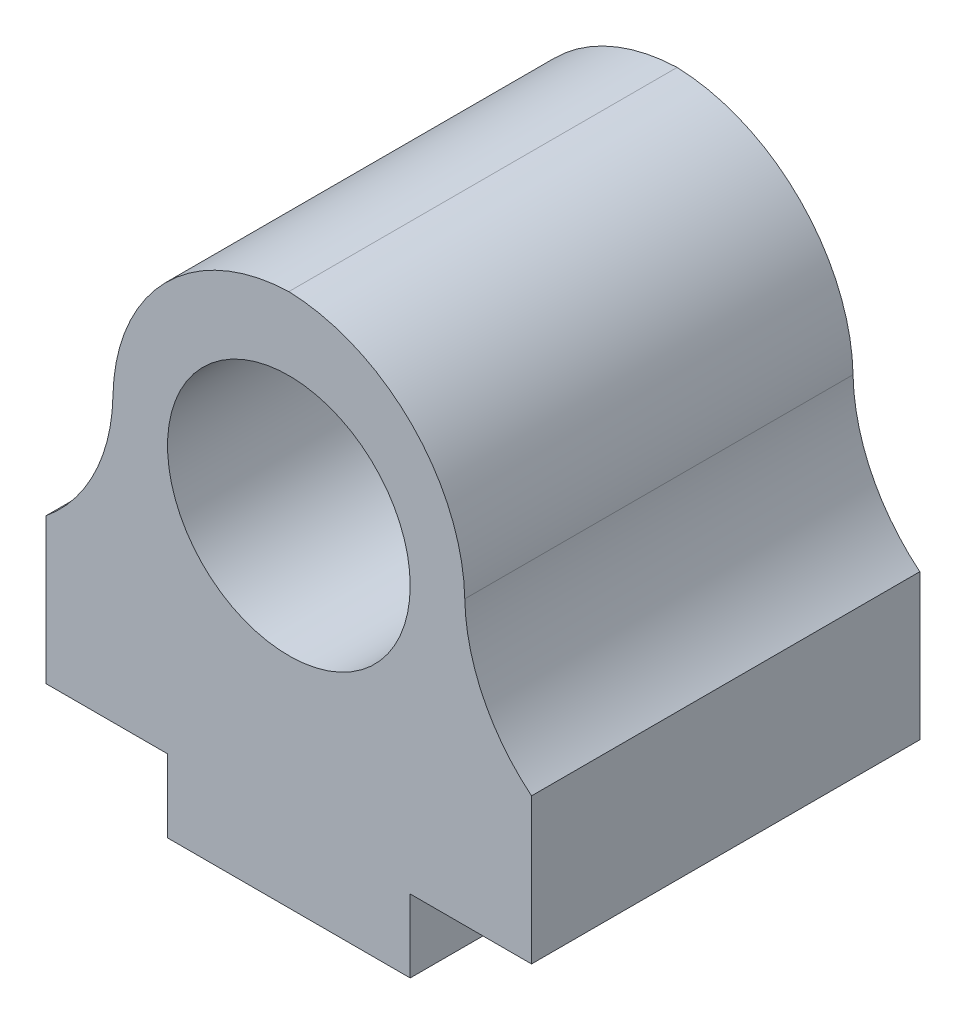
SolidWorks part; units mm, degrees
ref_plane "Front Plane" through (0, 0, 0) normal (0, 0, 1) x (1, 0, 0)
ref_plane "Top Plane" through (0, 0, 0) normal (0, 1, 0) x (1, 0, 0)
ref_plane "Right Plane" through (0, 0, 0) normal (1, 0, 0) x (0, 0, -1)
sketch "Sketch6" plane through (0, 0, 0) normal (0, 1, 0) x (1, 0, 0)
  line L1 (0, 0) -> (20, 0)
  line L2 (0, 0) -> (0, 16)
  line L3 (0, 16) -> (20, 16)
  line L4 (20, 0) -> (20, 16)
  dimension "D1" = 20
  dimension "D2" = 16
extrude "Boss-Extrude5" add sketch "Sketch6" along normal blind 6
sketch "Sketch7" plane through (0, 0, 0) normal (0, -1, 0) x (1, 0, 0)
  line L0 (0, 0) -> (20, 0) construction
  line L1 (5, 0) -> (15, 0)
  line L2 (5, 0) -> (5, -16)
  line L3 (5, -16) -> (15, -16)
  line L4 (15, 0) -> (15, -16)
  line L5 (20, -16) -> (0, -16) construction
  line L6 (0, -16) -> (0, 0) construction
  dimension "D1" = 10
  dimension "D2" = 5
extrude "Boss-Extrude6" add sketch "Sketch7" along normal blind 3
sketch "Sketch8" plane through (0, 6, 0) normal (0, 1, 0) x (1, 0, 0)
  line L0 (20, 16) -> (0, 16) construction
  line L1 (0, 0) -> (20, 0) construction
  line L2 (2.75, 16) -> (17.25, 16)
  line L3 (2.75, 16) -> (2.75, 0)
  line L4 (2.75, 0) -> (17.25, 0)
  line L5 (17.25, 16) -> (17.25, 0)
  line L6 (0, 16) -> (0, 0) construction
  dimension "D1" = 14.5
  dimension "D2" = 2.75
extrude "Boss-Extrude7" add sketch "Sketch8" along normal blind 13
sketch "Sketch9" plane through (0, 0, 0) normal (0, 0, 1) x (1, 0, 0)
  line L0 (2.75, 19) -> (2.75, 6) construction
  line L1 (2.75, 19) -> (17.25, 19) construction
  circle A0 centre (10, 11) radius 5
  dimension "D1" = 7.25
  dimension "D2" = 8
extrude "Cut-Extrude1" cut sketch "Sketch9" against normal through all
fillet "Fillet1" radius 7.5 2 edges at (17.25, 19, -8) (2.75, 19, -8)
fillet "Fillet2" radius 7.5 2 edges at (17.25, 6, -8) (2.75, 6, -8)
